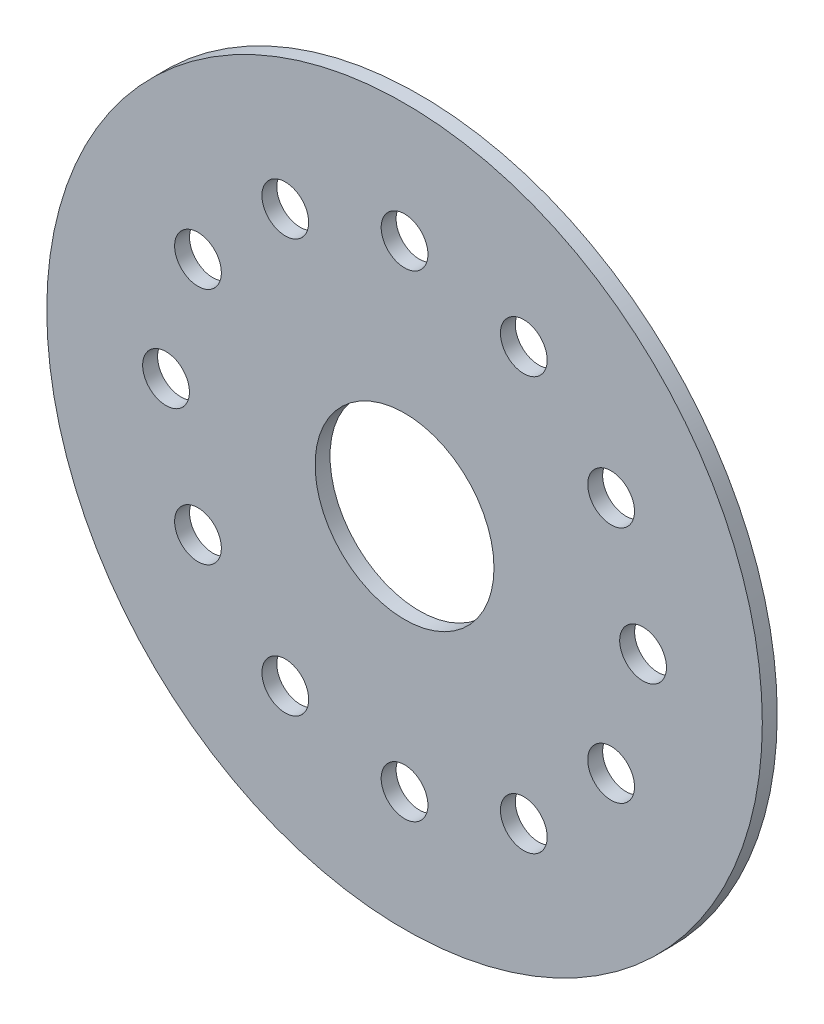
SolidWorks part; units mm, degrees
material "PC High Viscosity"
ref_plane "Front Plane" through (0, 0, 0) normal (0, 0, 1) x (1, 0, 0)
ref_plane "Top Plane" through (0, 0, 0) normal (0, 1, 0) x (1, 0, 0)
ref_plane "Right Plane" through (0, 0, 0) normal (1, 0, 0) x (0, 0, -1)
sketch "Sketch1" plane through (0, 0, 0) normal (0, 0, 1) x (1, 0, 0)
  circle A0 centre (0, 0) radius 9.525
  circle A1 centre (0, 0) radius 38.1
  circle A2 centre (0, 25.4) radius 2.4892
  circle A3 centre (12.7, 21.997) radius 2.4892
  circle A4 centre (21.997, 12.7) radius 2.4892
  circle A5 centre (25.4, 0) radius 2.4892
  circle A6 centre (21.997, -12.7) radius 2.4892
  circle A7 centre (12.7, -21.997) radius 2.4892
  circle A8 centre (0, -25.4) radius 2.4892
  circle A9 centre (-12.7, -21.997) radius 2.4892
  circle A10 centre (-21.997, -12.7) radius 2.4892
  circle A11 centre (-25.4, 0) radius 2.4892
  circle A12 centre (-21.997, 12.7) radius 2.4892
  circle A13 centre (-12.7, 21.997) radius 2.4892
  circle A14 centre (0, 0) radius 25.4 construction
  point P8 (-24.4671, 12.6655)
  point P30 (0, 0)
  point P31 (0, 0)
  dimension "D1" = 19.05
  dimension "D2" = 25.4
  dimension "D3" = 4.9784
  dimension "D5" = 12.7
  dimension "D4" = 12
extrude "Boss-Extrude1" add sketch "Sketch1" along normal blind 1.5875
